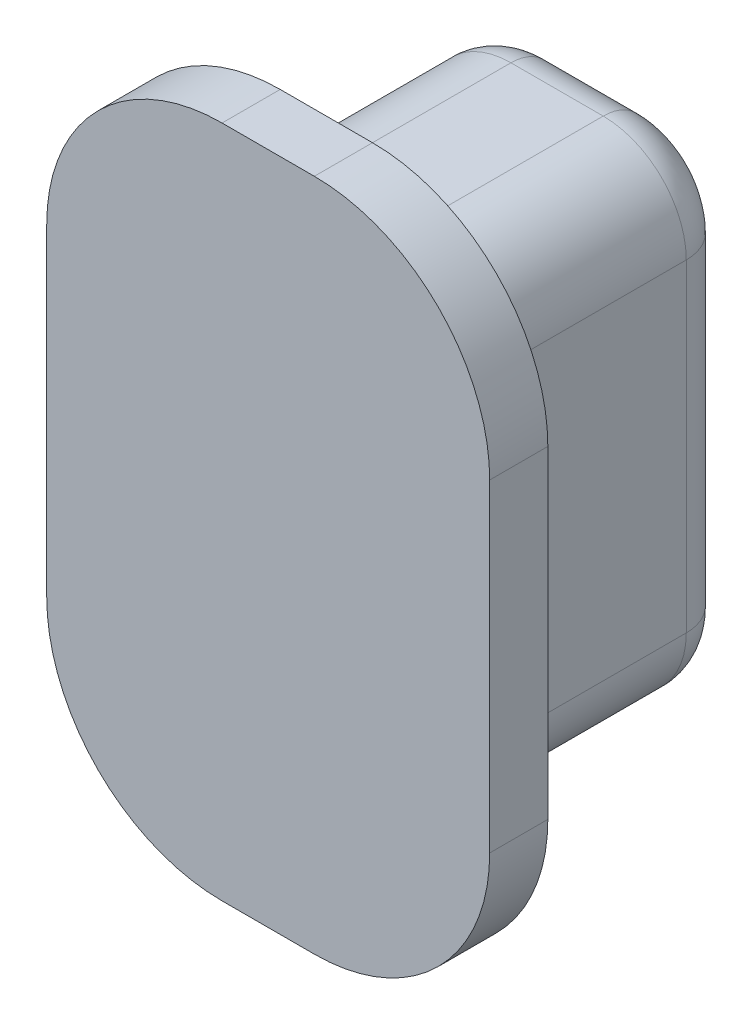
SolidWorks part; units mm, degrees
ref_plane "Front Plane" through (0, 0, 0) normal (0, 0, 1) x (1, 0, 0)
ref_plane "Top Plane" through (0, 0, 0) normal (0, 1, 0) x (1, 0, 0)
ref_plane "Right Plane" through (0, 0, 0) normal (1, 0, 0) x (0, 0, -1)
sketch "Sketch1" plane through (0, 0, 0) normal (0, 0, 1) x (1, 0, 0)
  line L0 (-3.5, 18.3) -> (-2.5, 18.3) construction
  line L1 (-4.5, 22.8) -> (-4.5, 19.3) construction
  line L2 (-1.5, 19.3) -> (-1.5, 22.8) construction
  line L3 (-2.5, 23.8) -> (-3.5, 23.8) construction
  line L4 (-3.5, 18.3) -> (-2.5, 18.3) construction
  line L5 (-2.5, 23.8) -> (-3.5, 23.8) construction
  line L6 (-1.5, 19.3) -> (-1.5, 22.8) construction
  line L7 (-4.5, 22.8) -> (-4.5, 19.3) construction
  line L8 (-3.5, 18.4) -> (-2.5, 18.4)
  line L9 (-1.6, 19.3) -> (-1.6, 22.8)
  line L10 (-2.5, 23.7) -> (-3.5, 23.7)
  line L11 (-4.4, 22.8) -> (-4.4, 19.3)
  arc A0 (-3.5, 23.8) -> (-4.5, 22.8) centre (-3.5, 22.8) ccw construction
  arc A1 (-4.5, 19.3) -> (-3.5, 18.3) centre (-3.5, 19.3) ccw construction
  arc A2 (-2.5, 18.3) -> (-1.5, 19.3) centre (-2.5, 19.3) ccw construction
  arc A3 (-1.5, 22.8) -> (-2.5, 23.8) centre (-2.5, 22.8) ccw construction
  arc A4 (-1.5, 22.8) -> (-2.5, 23.8) centre (-2.5, 22.8) ccw construction
  arc A5 (-2.5, 18.3) -> (-1.5, 19.3) centre (-2.5, 19.3) ccw construction
  arc A6 (-4.5, 19.3) -> (-3.5, 18.3) centre (-3.5, 19.3) ccw construction
  arc A7 (-3.5, 23.8) -> (-4.5, 22.8) centre (-3.5, 22.8) ccw construction
  arc A8 (-2.5, 18.4) -> (-1.6, 19.3) centre (-2.5, 19.3) ccw
  arc A9 (-1.6, 22.8) -> (-2.5, 23.7) centre (-2.5, 22.8) ccw
  arc A10 (-3.5, 23.7) -> (-4.4, 22.8) centre (-3.5, 22.8) ccw
  arc A11 (-4.4, 19.3) -> (-3.5, 18.4) centre (-3.5, 19.3) ccw
  point P5 (-3, 18.4)
  point P19 (-3, 23.7)
  point P26 (-4.4, 21.05)
  point P27 (-1.6, 21.05)
  dimension "D1" = 0.1
extrude "Boss-Extrude1" add sketch "Sketch1" against normal offset from surface (3 mm away) 0.5 offset beyond the face yes
sketch "Sketch2" plane through (0, 0, 0) normal (0, 0, 1) x (1, 0, 0)
  line L0 (-3.5, 17.4) -> (-2.5, 17.4)
  line L1 (-0.6, 19.3) -> (-0.6, 22.8)
  line L2 (-2.5, 24.7) -> (-3.5, 24.7)
  line L3 (-5.4, 22.8) -> (-5.4, 19.3)
  line L4 (-3.5, 18.4) -> (-2.5, 18.4)
  line L5 (-1.6, 19.3) -> (-1.6, 22.8)
  line L6 (-2.5, 23.7) -> (-3.5, 23.7)
  line L7 (-4.4, 22.8) -> (-4.4, 19.3)
  line L8 (-3.5, 18.4) -> (-2.5, 18.4) construction
  line L9 (-1.6, 19.3) -> (-1.6, 22.8) construction
  line L10 (-2.5, 23.7) -> (-3.5, 23.7) construction
  line L11 (-4.4, 22.8) -> (-4.4, 19.3) construction
  arc A0 (-5.4, 19.3) -> (-3.5, 17.4) centre (-3.5, 19.3) ccw
  arc A1 (-2.5, 17.4) -> (-0.6, 19.3) centre (-2.5, 19.3) ccw
  arc A2 (-0.6, 22.8) -> (-2.5, 24.7) centre (-2.5, 22.8) ccw
  arc A3 (-3.5, 24.7) -> (-5.4, 22.8) centre (-3.5, 22.8) ccw
  arc A4 (-4.4, 19.3) -> (-3.5, 18.4) centre (-3.5, 19.3) ccw
  arc A5 (-2.5, 18.4) -> (-1.6, 19.3) centre (-2.5, 19.3) ccw
  arc A6 (-1.6, 22.8) -> (-2.5, 23.7) centre (-2.5, 22.8) ccw
  arc A7 (-3.5, 23.7) -> (-4.4, 22.8) centre (-3.5, 22.8) ccw
  arc A8 (-4.4, 19.3) -> (-3.5, 18.4) centre (-3.5, 19.3) ccw construction
  arc A9 (-2.5, 18.4) -> (-1.6, 19.3) centre (-2.5, 19.3) ccw construction
  arc A10 (-1.6, 22.8) -> (-2.5, 23.7) centre (-2.5, 22.8) ccw construction
  arc A11 (-3.5, 23.7) -> (-4.4, 22.8) centre (-3.5, 22.8) ccw construction
  dimension "D1" = 0
  dimension "D2" = 1
extrude "Boss-Extrude2" add sketch "Sketch2" along normal offset from surface (0.63 mm away) 0.1
fillet "Fillet1" radius 0.5 8 edges at (-3, 18.4, -3) (-1.8636, 18.6636, -3) (-1.6, 21.05, -3) (-1.8636, 23.4364, -3) (-3, 23.7, -3) (-4.1364, 23.4364, -3) (-4.4, 21.05, -3) (-4.1364, 18.6636, -3)
